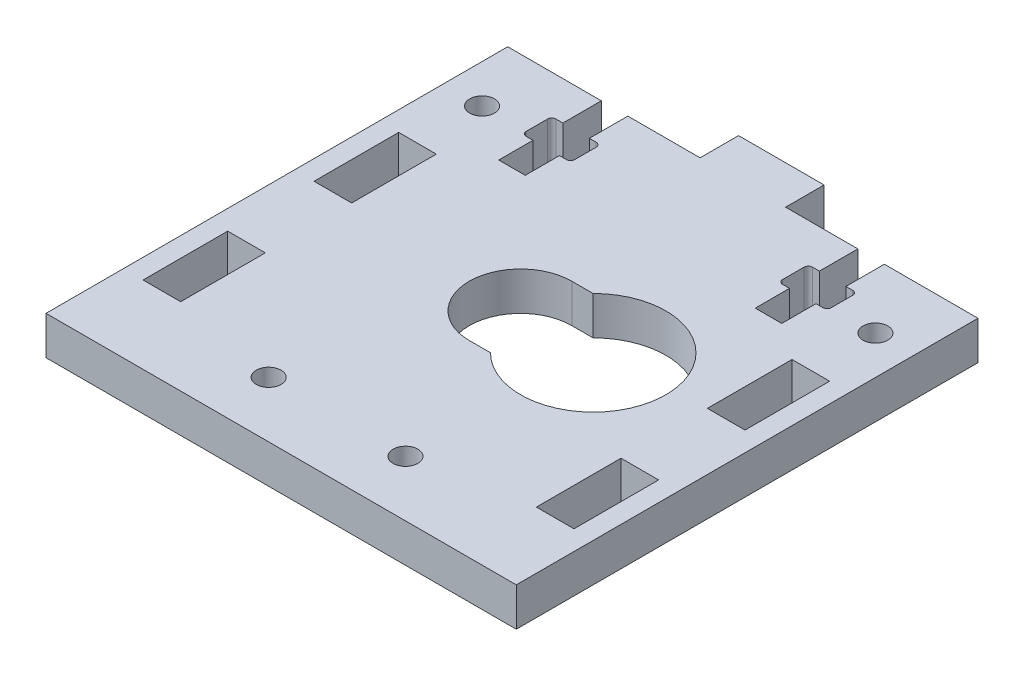
SolidWorks part; units mm, degrees
ref_plane "Front Plane" through (0, 0, 0) normal (0, 0, 1) x (1, 0, 0)
ref_plane "Top Plane" through (0, 0, 0) normal (0, 1, 0) x (1, 0, 0)
ref_plane "Right Plane" through (0, 0, 0) normal (1, 0, 0) x (0, 0, -1)
sketch "Sketch1" plane through (0, 0, 0) normal (0, 1, 0) x (1, 0, 0)
  line L1 (-27.5, 27) -> (27.5, 27)
  line L2 (-27.5, 27) -> (-27.5, -27)
  line L3 (-27.5, -27) -> (27.5, -27)
  line L4 (27.5, 27) -> (27.5, -27)
  line L5 (-27.5, 27) -> (27.5, -27) construction
  line L6 (-27.5, -27) -> (27.5, 27) construction
  point P0 (0, 0)
  dimension "D1" = 55
  dimension "D2" = 54
extrude "MainShape" add sketch "Sketch1" along normal blind 4.5
sketch "Sketch2" plane through (0, 4.5, 0) normal (0, 1, 0) x (1, 0, 0)
  line L0 (0, -27) -> (0, 27) construction
  line L1 (-27.5, -27) -> (27.5, -27) construction
  line L2 (27.5, 27) -> (-27.5, 27) construction
  line L4 (-5, 31.5) -> (5, 31.5)
  line L5 (-5, 31.5) -> (-5, 22.5)
  line L6 (-5, 22.5) -> (5, 22.5)
  line L7 (5, 31.5) -> (5, 22.5)
  line L8 (-5, 31.5) -> (5, 22.5) construction
  line L9 (-5, 22.5) -> (5, 31.5) construction
  dimension "D1" = 10
  dimension "D2" = 4.5
extrude "Tab1" add sketch "Sketch2" against normal through all
sketch "Sketch4" plane through (0, 4.5, 0) normal (0, 1, 0) x (1, 0, 0)
  line L0 (0, 31.5) -> (0, -27) construction
  line L1 (5, 31.5) -> (-5, 31.5) construction
  line L2 (-27.5, -27) -> (27.5, -27) construction
  line L3 (-15, 27) -> (-15, 15) construction
  line L4 (-5, 27) -> (-27.5, 27) construction
  line L5 (-13.45, 15) -> (-16.55, 15) construction
  line L6 (-16.55, 15) -> (-16.55, 27) construction
  line L7 (-13.45, 15) -> (-16.55, 15)
  line L8 (-16.55, 15) -> (-16.55, 19)
  line L9 (-16.55, 19) -> (-17.35, 19)
  line L10 (-17.85, 19.5) -> (-17.85, 22)
  line L11 (-17.35, 22.5) -> (-16.55, 22.5)
  line L12 (-16.55, 22.5) -> (-16.55, 27)
  line L13 (-16.55, 27) -> (-13.45, 27)
  line L14 (-13.45, 15) -> (-13.45, 27) construction
  line L15 (-13.45, 22.5) -> (-13.45, 27)
  line L16 (-12.65, 22.5) -> (-13.45, 22.5)
  line L17 (-12.15, 19.5) -> (-12.15, 22)
  line L18 (-13.45, 19) -> (-12.65, 19)
  line L19 (-13.45, 15) -> (-13.45, 19)
  line L20 (13.45, 15) -> (13.45, 27) construction
  line L21 (16.55, 15) -> (16.55, 27) construction
  line L22 (13.45, 15) -> (16.55, 15) construction
  line L23 (15, 27) -> (15, 15) construction
  line L24 (13.45, 15) -> (13.45, 19)
  line L25 (13.45, 19) -> (12.65, 19)
  line L26 (12.15, 19.5) -> (12.15, 22)
  line L27 (12.65, 22.5) -> (13.45, 22.5)
  line L28 (13.45, 22.5) -> (13.45, 27)
  line L29 (16.55, 27) -> (13.45, 27)
  line L30 (16.55, 22.5) -> (16.55, 27)
  line L31 (17.35, 22.5) -> (16.55, 22.5)
  line L32 (17.85, 19.5) -> (17.85, 22)
  line L33 (16.55, 19) -> (17.35, 19)
  line L34 (16.55, 15) -> (16.55, 19)
  line L35 (13.45, 15) -> (16.55, 15)
  arc A0 (-17.35, 19) -> (-17.85, 19.5) centre (-17.35, 19.5) cw
  arc A1 (-12.15, 19.5) -> (-12.65, 19) centre (-12.65, 19.5) cw
  arc A2 (-12.65, 22.5) -> (-12.15, 22) centre (-12.65, 22) cw
  arc A3 (-17.85, 22) -> (-17.35, 22.5) centre (-17.35, 22) cw
  arc A4 (17.85, 22) -> (17.35, 22.5) centre (17.35, 22) ccw
  arc A5 (12.65, 22.5) -> (12.15, 22) centre (12.65, 22) ccw
  arc A6 (12.15, 19.5) -> (12.65, 19) centre (12.65, 19.5) ccw
  arc A7 (17.35, 19) -> (17.85, 19.5) centre (17.35, 19.5) ccw
  point P24 (-17.85, 19)
  point P27 (-12.15, 19)
  point P30 (-12.15, 22.5)
  point P33 (-17.85, 22.5)
  point P56 (17.85, 22.5)
  point P57 (12.15, 22.5)
  point P58 (12.15, 19)
  point P59 (17.85, 19)
  dimension "D7" = 0.5
  dimension "D1" = 12
  dimension "D2" = 1.55
  dimension "D3" = 3.5
  dimension "D4" = 2.85
  dimension "D5" = 8
  dimension "D6" = 15
extrude "Cut-Extrude2" cut sketch "Sketch4" against normal through all
sketch "Sketch5" plane through (0, 4.5, 0) normal (0, 1, 0) x (1, 0, 0)
  line L0 (0, -27) -> (0, 31.5) construction
  line L1 (-27.5, -27) -> (27.5, -27) construction
  line L2 (5, 31.5) -> (-5, 31.5) construction
  line L3 (23, 27) -> (23, -27) construction
  line L4 (27.5, 27) -> (16.55, 27) construction
  line L5 (-23, 27) -> (-23, -27) construction
  line L6 (20.8, 11.95) -> (25.2, 11.95)
  line L7 (20.8, 11.95) -> (20.8, 2.05)
  line L8 (20.8, 2.05) -> (25.2, 2.05)
  line L9 (25.2, 11.95) -> (25.2, 2.05)
  line L10 (20.8, 11.95) -> (25.2, 2.05) construction
  line L11 (20.8, 2.05) -> (25.2, 11.95) construction
  line L12 (-20.8, 2.05) -> (-25.2, 11.95) construction
  line L13 (-20.8, 11.95) -> (-25.2, 2.05) construction
  line L14 (-25.2, 11.95) -> (-25.2, 2.05)
  line L15 (-20.8, 2.05) -> (-25.2, 2.05)
  line L16 (-20.8, 11.95) -> (-20.8, 2.05)
  line L17 (-20.8, 11.95) -> (-25.2, 11.95)
  line L18 (-27.5, -3) -> (27.5, -3) construction
  line L19 (-27.5, 27) -> (-27.5, -27) construction
  line L20 (27.5, -27) -> (27.5, 27) construction
  line L21 (-20.8, -17.95) -> (-25.2, -8.05) construction
  line L22 (-20.8, -8.05) -> (-25.2, -17.95) construction
  line L23 (20.8, -8.05) -> (25.2, -17.95) construction
  line L24 (20.8, -17.95) -> (25.2, -8.05) construction
  line L25 (-20.8, -17.95) -> (-25.2, -17.95)
  line L26 (-20.8, -17.95) -> (-20.8, -8.05)
  line L27 (-20.8, -8.05) -> (-25.2, -8.05)
  line L28 (-25.2, -17.95) -> (-25.2, -8.05)
  line L29 (25.2, -17.95) -> (25.2, -8.05)
  line L30 (20.8, -8.05) -> (25.2, -8.05)
  line L31 (20.8, -17.95) -> (20.8, -8.05)
  line L32 (20.8, -17.95) -> (25.2, -17.95)
  line L33 (-20.8, 11.95) -> (-25.2, 2.05) construction
  point P10 (23, 7)
  point P21 (-23, 7)
  point P36 (-23, -13)
  point P37 (23, -13)
  dimension "D1" = 23
  dimension "D2" = 9.9
  dimension "D3" = 4.4
  dimension "D4" = 20
  dimension "D5" = 20
extrude "Cut-Extrude3" cut sketch "Sketch5" against normal through all
sketch "Sketch6" plane through (0, 4.5, 0) normal (0, 1, 0) x (1, 0, 0)
  line L0 (0, -27) -> (0, 27) construction
  line L1 (5, 31.5) -> (-5, 31.5) construction
  line L3 (-27.5, 1) -> (27.5, 1) construction
  line L4 (-27.5, 27) -> (-27.5, -27) construction
  line L5 (27.5, -27) -> (27.5, 27) construction
  line L6 (27.5, 27) -> (16.55, 27) construction
  line L7 (-27.5, -27) -> (27.5, -27) construction
  line L9 (-27.5, 27) -> (27.5, 27) construction
  circle A0 centre (0, 1) radius 12
  point P4 (0, 31.5)
  dimension "D1" = 24
  dimension "D2" = 26
extrude "Cut-Extrude4" cut sketch "Sketch6" against normal through all
sketch "Sketch7" plane through (0, 4.5, 0) normal (0, 1, 0) x (1, 0, 0)
  line L0 (0, 1) -> (0, -27) construction
  line L3 (-27.5, -27) -> (27.5, -27) construction
  line L4 (8, -20.46) -> (-8, -20.46) construction
  circle A1 centre (-8, -20.46) radius 1.45
  circle A2 centre (8, -20.46) radius 1.45
  point P8 (0, -20.46)
  dimension "D1" = 2.9
  dimension "D3" = 21.46
extrude "Cut-Extrude5" [suppressed] cut sketch "Sketch7" against normal through all
sketch "Sketch8" plane through (0, 4.5, 0) normal (0, 1, 0) x (1, 0, 0)
  line L0 (-12, 1) -> (12, 1) construction
  line L1 (0, 1) -> (0, -20.46) construction
  line L2 (8, -20.46) -> (-8, -20.46) construction
  line L3 (0, -11) -> (0, 13) construction
  circle A0 centre (-8, -20.46) radius 1.45
  circle A1 centre (0, 1) radius 12 construction
  circle A2 centre (8, -20.46) radius 1.45
  dimension "D3" = 2.9
  dimension "D1" = 90
  dimension "D4" = 21.46
extrude "Cut-Extrude6" cut sketch "Sketch8" against normal through all
sketch "Sketch9" plane through (0, 4.5, 0) normal (0, 1, 0) x (1, 0, 0)
  line L0 (0, -27) -> (0, 31.5) construction
  line L1 (-27.5, -27) -> (27.5, -27) construction
  line L2 (5, 31.5) -> (-5, 31.5) construction
  line L3 (16, -27) -> (16, -16) construction
  line L4 (14.45, -16) -> (17.55, -16) construction
  line L5 (17.55, -16) -> (17.55, -27) construction
  line L6 (17.55, -27) -> (17.55, -22.5)
  line L7 (17.55, -22.5) -> (18.35, -22.5)
  line L8 (18.85, -22) -> (18.85, -19.5)
  line L9 (18.35, -19) -> (17.55, -19)
  line L10 (17.55, -19) -> (17.55, -16)
  line L11 (17.55, -16) -> (14.45, -16)
  line L12 (17.55, -27) -> (14.45, -27)
  line L13 (14.45, -16) -> (14.45, -27) construction
  line L14 (14.45, -19) -> (14.45, -16)
  line L15 (13.65, -19) -> (14.45, -19)
  line L16 (13.15, -22) -> (13.15, -19.5)
  line L17 (14.45, -22.5) -> (13.65, -22.5)
  line L18 (14.45, -27) -> (14.45, -22.5)
  line L19 (-14.45, -16) -> (-14.45, -27) construction
  line L20 (-17.55, -16) -> (-17.55, -27) construction
  line L21 (-14.45, -16) -> (-17.55, -16) construction
  line L22 (-16, -27) -> (-16, -16) construction
  line L23 (-14.45, -27) -> (-14.45, -22.5)
  line L24 (-14.45, -22.5) -> (-13.65, -22.5)
  line L25 (-13.15, -22) -> (-13.15, -19.5)
  line L26 (-13.65, -19) -> (-14.45, -19)
  line L27 (-14.45, -19) -> (-14.45, -16)
  line L28 (-17.55, -27) -> (-14.45, -27)
  line L29 (-17.55, -16) -> (-14.45, -16)
  line L30 (-17.55, -19) -> (-17.55, -16)
  line L31 (-18.35, -19) -> (-17.55, -19)
  line L32 (-18.85, -22) -> (-18.85, -19.5)
  line L33 (-17.55, -22.5) -> (-18.35, -22.5)
  line L34 (-17.55, -27) -> (-17.55, -22.5)
  arc A0 (18.35, -22.5) -> (18.85, -22) centre (18.35, -22) ccw
  arc A1 (18.85, -19.5) -> (18.35, -19) centre (18.35, -19.5) ccw
  arc A2 (13.15, -19.5) -> (13.65, -19) centre (13.65, -19.5) cw
  arc A3 (13.65, -22.5) -> (13.15, -22) centre (13.65, -22) cw
  arc A4 (-13.65, -22.5) -> (-13.15, -22) centre (-13.65, -22) ccw
  arc A5 (-13.15, -19.5) -> (-13.65, -19) centre (-13.65, -19.5) ccw
  arc A6 (-18.85, -19.5) -> (-18.35, -19) centre (-18.35, -19.5) cw
  arc A7 (-18.35, -22.5) -> (-18.85, -22) centre (-18.35, -22) cw
  point P16 (18.85, -22.5)
  point P19 (18.85, -19)
  point P30 (13.15, -19)
  point P31 (13.15, -22.5)
  point P54 (-13.15, -22.5)
  point P55 (-13.15, -19)
  point P56 (-18.85, -19)
  point P57 (-18.85, -22.5)
  dimension "D7" = 0.5
  dimension "D2" = 1.55
  dimension "D1" = 11
  dimension "D3" = 8
  dimension "D4" = 3.5
  dimension "D5" = 2.85
  dimension "D6" = 16
extrude "Cut-Extrude7" [suppressed] cut sketch "Sketch9" against normal through all
sketch "Sketch10" [suppressed] plane through (0, 0, 27) normal (0, 0, 1) x (1, 0, 0)
  line L0 (-27.5, 2.25) -> (27.5, 2.25) construction
  line L1 (-27.5, 4.5) -> (-27.5, 0) construction
  line L2 (27.5, 4.5) -> (27.5, 0) construction
  line L3 (-16, 4.5) -> (-16, 0) construction
  line L4 (-14.25, 4.5) -> (-17.75, 4.5) construction
  line L5 (16, 4.5) -> (16, 0) construction
  line L6 (17.75, 4.5) -> (14.25, 4.5) construction
  line L7 (17.75, 0) -> (14.25, 0) construction
  line L8 (-14.25, 0) -> (-17.75, 0) construction
  circle A0 centre (-16, 2.25) radius 1.6
  circle A1 centre (16, 2.25) radius 1.6
  dimension "D1" = 3.2
  dimension "D2" = 3.2
sketch "Sketch11" plane through (0, 4.5, 0) normal (0, 1, 0) x (1, 0, 0)
  line L0 (-20.8, 7) -> (-25.2, 7) construction
  line L1 (-20.8, 2.05) -> (-20.8, 11.95) construction
  line L2 (-25.2, 11.95) -> (-25.2, 2.05) construction
  line L3 (-23, 7) -> (-23, 27) construction
  line L4 (-16.55, 27) -> (-27.5, 27) construction
  line L5 (0, 31.5) -> (0, 0) construction
  line L6 (5, 31.5) -> (-5, 31.5) construction
  line L7 (23, 7) -> (23, 27) construction
  line L8 (20.8, 7) -> (25.2, 7) construction
  line L9 (-23, 7) -> (-23, 27) construction
  circle A0 centre (-23, 19.5) radius 1.45
  circle A1 centre (23, 19.5) radius 1.45
  dimension "D1" = 2.9
  dimension "D2" = 7.5
extrude "Cut-Extrude8" cut sketch "Sketch11" against normal through all
sketch "Sketch12" [suppressed] plane through (0, 4.5, 0) normal (0, 1, 0) x (1, 0, 0)
  line L0 (-27.5, -7) -> (-34, -17)
  line L1 (-27.5, 27) -> (-27.5, -27) construction
  line L2 (-34, -17) -> (-34, -27)
  line L3 (-34, -27) -> (-27.5, -27)
  line L4 (-27.5, -27) -> (-27.5, -7)
  line L5 (-27.5, -27) -> (27.5, -27) construction
  line L6 (0, -27) -> (0, 31.5) construction
  line L7 (5, 31.5) -> (-5, 31.5) construction
  line L8 (27.5, -27) -> (27.5, -7)
  line L9 (34, -27) -> (27.5, -27)
  line L10 (34, -17) -> (34, -27)
  line L11 (27.5, -7) -> (34, -17)
  point P4 (0, -27)
  dimension "D1" = 34
  dimension "D2" = 10
  dimension "D3" = 20
extrude "Boss-Extrude1" [suppressed] add sketch "Sketch12" against normal through all
sketch "Sketch14" [suppressed] plane through (0, 4.5, 0) normal (0, 1, 0) x (1, 0, 0)
  line L0 (-34, -27) -> (34, -27) construction
  line L2 (-34, -27) -> (34, -27) construction
  line L3 (0, -27) -> (0, 31.5) construction
  line L4 (5, 31.5) -> (-5, 31.5) construction
  line L6 (26.25, -16.5) -> (26.25, -27) construction
  line L8 (-28, -27) -> (-28, -16.5) construction
  line L9 (-26.25, -16.5) -> (-29.75, -16.5) construction
  line L10 (-29.75, -16.5) -> (-29.75, -27) construction
  line L11 (-26.25, -27) -> (-29.75, -27)
  line L12 (-29.75, -27) -> (-29.75, -23.2)
  line L13 (-29.75, -23.2) -> (-30.75, -23.2)
  line L14 (-31, -22.95) -> (-31, -19.25)
  line L15 (-30.75, -19) -> (-29.75, -19)
  line L16 (-29.75, -19) -> (-29.75, -16.5)
  line L17 (-29.75, -16.5) -> (-26.25, -16.5)
  line L18 (-26.25, -16.5) -> (-26.25, -27) construction
  line L19 (-26.25, -19) -> (-26.25, -16.5)
  line L20 (-25.25, -19) -> (-26.25, -19)
  line L21 (-25, -22.95) -> (-25, -19.25)
  line L22 (-26.25, -23.2) -> (-25.25, -23.2)
  line L23 (-26.25, -27) -> (-26.25, -23.2)
  line L24 (29.75, -16.5) -> (29.75, -27) construction
  line L25 (26.25, -16.5) -> (29.75, -16.5) construction
  line L26 (28, -27) -> (28, -16.5) construction
  line L27 (26.25, -27) -> (26.25, -23.2)
  line L28 (26.25, -23.2) -> (25.25, -23.2)
  line L29 (25, -22.95) -> (25, -19.25)
  line L30 (25.25, -19) -> (26.25, -19)
  line L31 (26.25, -19) -> (26.25, -16.5)
  line L32 (29.75, -16.5) -> (26.25, -16.5)
  line L33 (29.75, -19) -> (29.75, -16.5)
  line L34 (30.75, -19) -> (29.75, -19)
  line L35 (31, -22.95) -> (31, -19.25)
  line L36 (29.75, -23.2) -> (30.75, -23.2)
  line L37 (29.75, -27) -> (29.75, -23.2)
  line L38 (26.25, -27) -> (29.75, -27)
  line L39 (-26.25, -16.5) -> (-26.25, -27) construction
  arc A0 (-30.75, -23.2) -> (-31, -22.95) centre (-30.75, -22.95) cw
  arc A1 (-31, -19.25) -> (-30.75, -19) centre (-30.75, -19.25) cw
  arc A2 (-25, -19.25) -> (-25.25, -19) centre (-25.25, -19.25) ccw
  arc A3 (-25.25, -23.2) -> (-25, -22.95) centre (-25.25, -22.95) ccw
  arc A4 (25.25, -23.2) -> (25, -22.95) centre (25.25, -22.95) cw
  arc A5 (25, -19.25) -> (25.25, -19) centre (25.25, -19.25) cw
  arc A6 (31, -19.25) -> (30.75, -19) centre (30.75, -19.25) ccw
  arc A7 (30.75, -23.2) -> (31, -22.95) centre (30.75, -22.95) ccw
  point P2 (0, -27)
  dimension "D10" = 0.5
  dimension "D4" = 1.55
  dimension "D6" = 11
  dimension "D2" = 28
  dimension "D3" = 2.85
  dimension "D5" = 3.5
  dimension "D7" = 8
extrude "Cut-Extrude9" [suppressed] cut sketch "Sketch14" against normal through all
sketch "Sketch15" plane through (0, 4.5, 0) normal (0, 1, 0) x (1, 0, 0)
  circle A0 centre (0, 1) radius 12
  circle A1 centre (0, 1) radius 6
  circle A2 centre (0, 1) radius 12 construction
  dimension "D1" = 12
extrude "Boss-Extrude2" add sketch "Sketch15" against normal through all
sketch "Sketch16" plane through (0, 4.5, 0) normal (0, 1, 0) x (1, 0, 0)
  line L0 (0, 1) -> (27.5, 1) construction
  line L1 (27.5, -27) -> (27.5, 27) construction
  line L2 (0, 7) -> (2.4792, 7)
  line L3 (0, -5) -> (2.4792, -5)
  line L4 (0, 7) -> (0, -5)
  arc A0 (2.4792, -5) -> (2.4792, 7) centre (8.5, 1) ccw
  circle A1 centre (0, 1) radius 6 construction
  dimension "D1" = 17
  dimension "D2" = 8.5
extrude "Cut-Extrude10" cut sketch "Sketch16" against normal through all
equation "\"X-ROD-SPACING\"=45"
equation "\"Y-ROD-SPACING\"=75"
equation "\"Z-ROD-SPACING\"=17.5"
equation "\"Y-BED-OFFSET\"=2"
equation "\"Y-BED-ROD-INSET\"=3.5"
equation "\"Y-BED-SCREW-SPACING\"=209"
equation "\"Y-BED-SCREW-CUTOUT-SLOT-HEIGHT\"=2"
equation "\"T-SLOT-NUT-FILLET-RADIUS\"=0.5"
equation "\"T-SLOT-SCREW-SHAFT-RADIUS\"=1.55"
equation "\"T-SLOT-SCREW-SHAFT-CUTOUT-LENGTH\"=11.0"
equation "\"T-SLOT-NUT-DEPTH\"=3.5"
equation "\"T-SLOT-NUT-WIDTH\"=2.85"
equation "\"T-SLOT-NUT-END-DISTANCE\"=8"
equation "\"ACRYLIC-THICKNESS\"=10"
equation "\"ACRYLIC-THICKNESS2\"=4.5"
equation "\"ACRYLIC-TAB-CUTOUT-SIZE\"=\"ACRYLIC-THICKNESS\"+\"ACRYLIC-TAB-TOLERANCE\"*2"
equation "\"ACRYLIC-TAB-WIDTH\"=\"ACRYLIC-THICKNESS\""
equation "\"ACRYLIC-M3-HOLE\"=2.9"
equation "\"SMOOTHROD-CAP-SCREW-DISTANCE\"=20"
equation "\"FRAME-WIDTH-INNER\"=370"
equation "\"NEMA17-HOLE-SPACING\"=31"
equation "\"NEMA17-CENTRAL-CUTOUT\"=22.5"
equation "\"Z-BRACKET-REACH\"=55"
equation "\"Z-ROD-INSET\"=16"
equation "\"TOP-BRACKET-SPACING\"=40"
equation "\"SMOOTHROD-X-LENGTH\"=350"
equation "\"SMOOTHROD-Y-LENGTH\"=350"
equation "\"SMOOTHROD-Z-LENGTH\"=350"
equation "\"SMOOTHROD-TIGHTENING-HEADROOM\"=.25"
equation "\"LEADSCREW-Z-LENGTH\"=300"
equation "\"SCREW-LENGTH-FRAME\"=\"ACRYLIC-THICKNESS\" + 10"
equation "\"SCREW-LENGTH-MOTOR\"=\"ACRYLIC-THICKNESS\" + 5"
equation "\"SCREW-LENGTH-EXTRUDER\"=28"
equation "\"SCREW-HEAD-RADIUS\"=6"
equation "\"PRINTED-X-SMOOTHROD-DIAMETER\"=8.4"
equation "\"PRINTED-X-SMOOTHROD-CUTOUT\"=10"
equation "\"PRINTED-X-BASE-HEIGHT\"=10"
equation "\"PRINTED-LM8UU-CUTOUT-SIZE\"=15.5"
equation "\"PRINTED-LM8UU-CUTOUT-LENGTH\"=24.5"
equation "\"PRINTED-X-IDLER-HEIGHT\"=16"
equation "\"PSU-MOUNTING-WIDTH\"=95"
equation "\"PSU-MOUNTING-HEIGHT\"=177"
equation "\"Y-BELT-TO-ROD-DISTANCE\"=20"
equation "\"SPOOL-HOLDER-ROD-SPACING\"=150"
equation "\"ACRYLIC-X-CARRIAGE-WIDTH\"=55"
equation "\"ACRYLIC-X-CARRIAGE-HEIGHT\"=75"
equation "\"ACRYLIC-X-CARRIAGE-SCREW-SPACING-X\"=15"
equation "\"ACRYLIC-X-CARRIAGE-SCREW-SPACING-Y\"=33"
equation "\"ACRYLIC-X-CARRIAGE-CENTER-TAB-SPACING\"=14"
equation "\"D1@Sketch1\"=\"ACRYLIC-X-CARRIAGE-WIDTH\""
equation "\"D1@MainShape\" = \"ACRYLIC-THICKNESS2\""
equation "\"D1@Sketch2\"=\"ACRYLIC-TAB-WIDTH\""
equation "\"D2@Sketch2\"=\"ACRYLIC-THICKNESS2\""
equation "\"D1@Sketch4\"=\"T-SLOT-SCREW-SHAFT-CUTOUT-LENGTH\"+1"
equation "\"D2@Sketch4\"=\"T-SLOT-SCREW-SHAFT-RADIUS\""
equation "\"D3@Sketch4\"=\"T-SLOT-NUT-DEPTH\""
equation "\"D4@Sketch4\"=\"T-SLOT-NUT-WIDTH\""
equation "\"D5@Sketch4\"=\"T-SLOT-NUT-END-DISTANCE\""
equation "\"D6@Sketch4\"=\"ACRYLIC-X-CARRIAGE-SCREW-SPACING-X\""
equation "\"D7@Sketch4\"=\"T-SLOT-NUT-FILLET-RADIUS\""
equation "\"ACRYLIC-X-CARRIAGE-EXTRUDER-SHELF-DEPTH\"=\"ACRYLIC-X-CARRIAGE-EXTRUDER-OFFSET\" + 28"
equation "\"D2@Sketch1\"=\"ACRYLIC-X-CARRIAGE-EXTRUDER-SHELF-DEPTH\""
equation "\"ACRYLIC-X-CARRIAGE-LM8UU-CUTOUT-WIDTH\"=24.25"
equation "\"ACRYLIC-X-CARRIAGE-EXTRUDER-BRACE-SPACING\"=23"
equation "\"ACRYLIC-X-CARRIAGE-EXTRUDER-BRACE-TAB-OFFSET\"=20"
equation "\"ACRYLIC-X-CARRIAGE-EXTRUDER-BRACE-HEIGHT\"=35"
equation "\"ACRYLIC-X-CARRIAGE-EXTRUDER-BRACE-SCREW-SPACING\"=22"
equation "\"D1@Sketch5\"=\"ACRYLIC-X-CARRIAGE-EXTRUDER-BRACE-SPACING\""
equation "\"D2@Sketch5\"=\"ACRYLIC-TAB-WIDTH\"-\"KERF\"*2"
equation "\"D3@Sketch5\"=\"ACRYLIC-THICKNESS2\"-\"KERF\"*2"
equation "\"D4@Sketch5\"=\"ACRYLIC-X-CARRIAGE-EXTRUDER-BRACE-TAB-OFFSET\""
equation "\"D1@Sketch7\"=\"ACRYLIC-M3-HOLE\""
equation "\"D3@Sketch8\"=\"ACRYLIC-M3-HOLE\""
equation "\"ACRYLIC-X-CARRIAGE-EXTRUDER-ANGLE\"=90"
equation "\"D1@Sketch8\"=\"ACRYLIC-X-CARRIAGE-EXTRUDER-ANGLE\""
equation "\"ACRYLIC-X-CARRIAGE-EXTRUDER-OFFSET\"=26"
equation "\"D2@Sketch6\"=\"ACRYLIC-X-CARRIAGE-EXTRUDER-OFFSET\""
equation "\"D1@Sketch9\"=\"T-SLOT-SCREW-SHAFT-CUTOUT-LENGTH\""
equation "\"D2@Sketch9\"=\"T-SLOT-SCREW-SHAFT-RADIUS\""
equation "\"D3@Sketch9\"=\"T-SLOT-NUT-END-DISTANCE\""
equation "\"D4@Sketch9\"=\"T-SLOT-NUT-DEPTH\""
equation "\"D5@Sketch9\"=\"T-SLOT-NUT-WIDTH\""
equation "\"D7@Sketch9\"=\"T-SLOT-NUT-FILLET-RADIUS\""
equation "\"ACRYLIC-TAB-TOLERANCE\"=-.05"
equation "\"D1@Sketch11\"=\"ACRYLIC-M3-HOLE\""
equation "\"D6@Sketch14\"=\"T-SLOT-SCREW-SHAFT-CUTOUT-LENGTH\""
equation "\"D3@Sketch14\"=\"T-SLOT-NUT-WIDTH\""
equation "\"D5@Sketch14\"=\"T-SLOT-NUT-DEPTH\""
equation "\"D4@Sketch14\"=\"T-SLOT-SCREW-SHAFT-RADIUS\""
equation "\"D10@Sketch14\"=\"T-SLOT-NUT-FILLET-RADIUS\""
equation "\"D7@Sketch14\"=\"T-SLOT-NUT-END-DISTANCE\""
equation "\"KERF\"=0.05"
equation "\"PRINTED-M3-HOLE\"=3.5"
equation "\"PRINTED-M3-NUT-AF\"=6.25"
equation "\"ACRYLIC-X-CARRIAGE-LM8UU-CUTOUT-HEIGHT\"=11.0"
equation "\"ACRYLIC-X-CARRIAGE-DUAL-WIDTH-MULTIPLIER\"=1.65"
equation "\"ACRYLIC-X-CARRIAGE-DUAL-HOTEND-SPACING\"=42"
equation "\"ACRYLIC-X-CARRIAGE-DUAL-WIDTH\"=75"
equation "\"ACRYLIC-X-CARRIAGE-DUAL-FAN-OFFSET\"=52"
equation "\"ACRYLIC-X-CARRIAGE-DUAL-FAN-HEIGHT\"=20"
equation "\"ACRYLIC-X-CARRIAGE-DUAL-HOTEND-SEPARATION\"=36"
equation "\"ACRYLIC-X-CARRIAGE-DUAL-MOUNT-PLATE-DEPTH\"=75"
equation "\"ACRYLIC-X-CARRIAGE-DUAL-MOUNT-BRACE-WIDTH\"=33"
equation "\"ACRYLIC-X-CARRIAGE-DUAL-MOUNT-SCREW-WIDTH\"=40"
equation "\"BLOWER-FAN-WIDTH\"=15"
